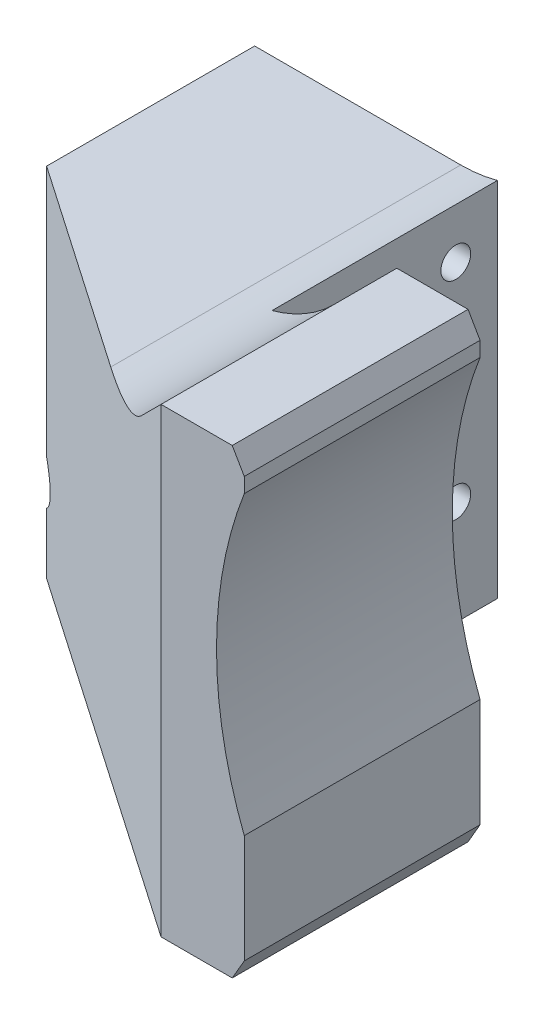
SolidWorks part; units mm, degrees
material "Rubber"
ref_plane "Front Plane" through (0, 0, 0) normal (0, 0, 1) x (1, 0, 0)
ref_plane "Top Plane" through (0, 0, 0) normal (0, 1, 0) x (1, 0, 0)
ref_plane "Right Plane" through (0, 0, 0) normal (1, 0, 0) x (0, 0, -1)
sketch "Sketch1" plane through (0, 0, 0) normal (0, 1, 0) x (1, 0, 0)
  line L0 (0, 0) -> (35, 0)
  line L1 (35, 0) -> (35, -32.5)
  line L2 (35, -32.5) -> (65, -32.5)
  line L3 (65, -32.5) -> (65, -66.5)
  line L4 (65, -66.5) -> (53, -66.5)
  line L5 (53, -66.5) -> (0, -30)
  line L6 (0, -30) -> (0, 0)
  dimension "D1" = 35
  dimension "D2" = 30
  dimension "D3" = 12
  dimension "D4" = 32.5
  dimension "D5" = 34
  dimension "D6" = 30
extrude "Boss-Extrude1" add sketch "Sketch1" along normal blind 51.5
sketch "Sketch3" plane through (35, 0, 0) normal (1, 0, 0) x (0, 0, -1)
  line L2 (-32.5, 0) -> (0, 0) construction
  circle A1 centre (-26.15, 12) radius 5
  dimension "D5" = 10
  dimension "D4" = 12
extrude "Cut-Extrude1" cut sketch "Sketch3" against normal through all
sketch "Sketch4" plane through (0, 0, 0) normal (0, 0, -1) x (-1, 0, 0)
  line L0 (0, 8) -> (-1, 8)
  line L1 (0, 51.5) -> (0, 0) construction
  line L2 (-6, 3) -> (-6, 0)
  line L3 (-35, 0) -> (0, 0) construction
  line L4 (-6, 0) -> (0, 0)
  line L5 (0, 0) -> (0, 8)
  arc A0 (-6, 3) -> (-1, 8) centre (-1, 3) cw
  point P11 (-6, 8)
  dimension "D3" = 5
  dimension "D1" = 8
  dimension "D2" = 6
extrude "Cut-Extrude2" [suppressed] cut sketch "Sketch4" against normal blind 10
sketch "Sketch5" plane through (0, 51.5, 0) normal (0, 1, 0) x (1, 0, 0)
  line L0 (65, -32.5) -> (35, -32.5) construction
  line L1 (65, -66.5) -> (53, -66.5)
  line L2 (65, -66.5) -> (65, -32.5)
  line L3 (65, -32.5) -> (53, -32.5)
  line L4 (53, -66.5) -> (53, -32.5)
  point P7 (70, -66.5)
extrude "Boss-Extrude2" add sketch "Sketch5" along normal blind 15
chamfer "Chamfer1" distance 15 angle 45 1 edges at (53, 51.5, 49.5)
sketch "Sketch6" plane through (0, 0, 66.5) normal (0, 0, 1) x (1, 0, 0)
  line L0 (65, 66.5) -> (65, 0) construction
  line L1 (53, 0) -> (65, 0) construction
  circle A0 centre (120, 40) radius 59
  dimension "D2" = 118
  dimension "D1" = 55
  dimension "D3" = 40
extrude "Cut-Extrude3" cut sketch "Sketch6" against normal through all
sketch "Sketch7" plane through (0, 0, 0) normal (-1, 0, 0) x (0, 0, 1)
  line L0 (0, 51.5) -> (0, 0) construction
  line L1 (0, 0) -> (30, 0) construction
  circle A0 centre (6, 15) radius 2.15
  circle A1 centre (6, 45) radius 2.15
  dimension "D1" = 4.3
  dimension "D5" = 4.3
  dimension "D2" = 6
  dimension "D3" = 15
  dimension "D4" = 45
extrude "Cut-Extrude4" cut sketch "Sketch7" against normal through all
sketch "Sketch8" plane through (0, 0, 0) normal (-1, 0, 0) x (0, 0, 1)
  line L0 (0, 51.5) -> (0, 0) construction
  circle A0 centre (6, 45) radius 4.5
  circle A1 centre (6, 15) radius 4.5
  dimension "D1" = 9
  dimension "D2" = 9
extrude "Cut-Extrude5" cut sketch "Sketch8" against normal blind 25
fillet "Fillet1" radius 20 1 edges at (38, 51.5, 44.3349)
chamfer "Chamfer3" distance 3 angle 30 2 edges at (65, 0, 49.5) (65, 66.5, 49.5) first distance on face at (65, 9.3229, 49.5) first distance on face at (65, 63.9271, 49.5)
